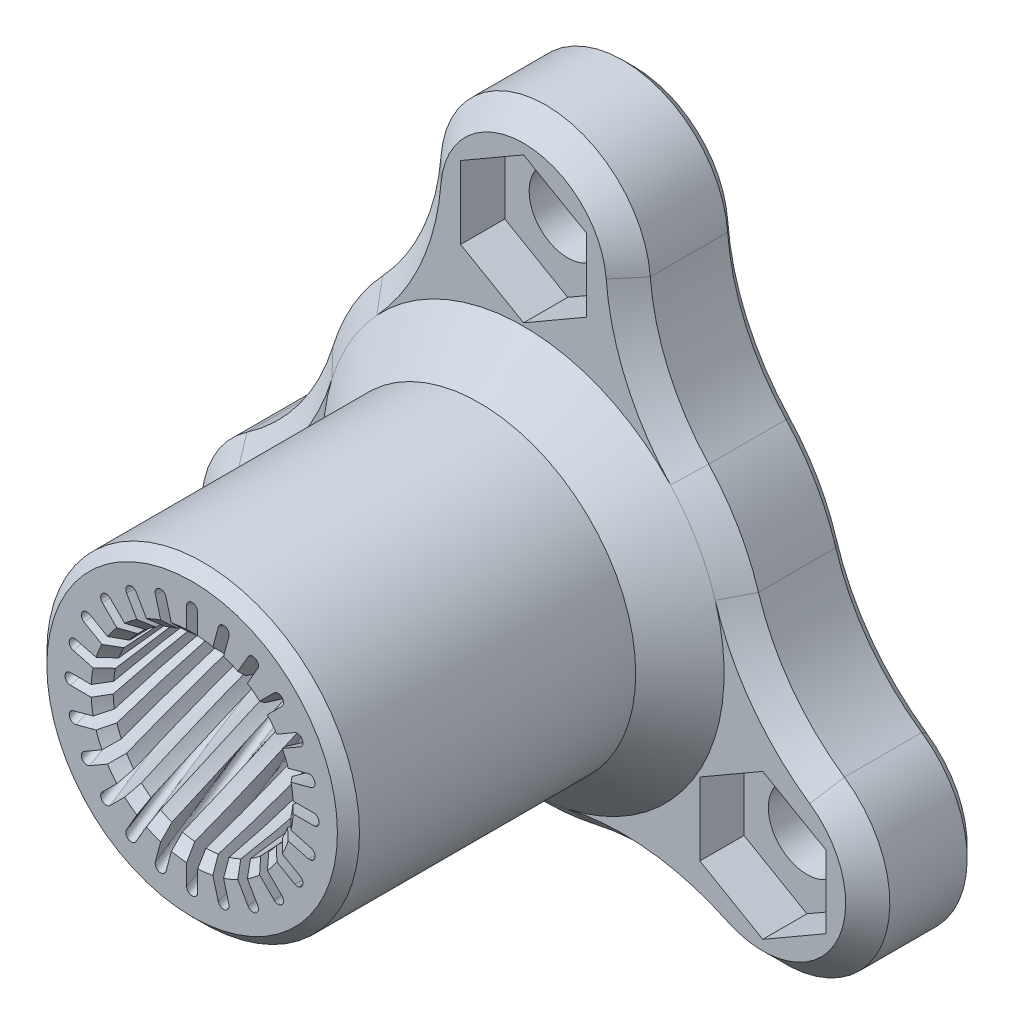
SolidWorks part; units mm, degrees
note: '?' marks a value the reader was unsure of.
ref_plane "Front Plane" through (0, 0, 0) normal (0, 0, 1) x (1, 0, 0)
ref_plane "Top Plane" through (0, 0, 0) normal (0, 1, 0) x (1, 0, 0)
ref_plane "Right Plane" through (0, 0, 0) normal (1, 0, 0) x (0, 0, -1)
sketch "Sketch1" plane through (0, 0, 0) normal (0, 0, 1) x (1, 0, 0)
  circle A0 centre (0, 0) radius 4.075
  circle A1 centre (0, 0) radius 7.075
  dimension "D1" = 8.15
  dimension "D2" = 3
extrude "Boss-Extrude1" add sketch "Sketch1" along normal blind 20
sketch "Sketch2" plane through (0, 0, 20) normal (0, 0, 1) x (1, 0, 0)
  circle A0 centre (0, 0) radius 4
curve "Helix/Spiral1" pitch 100 height 20 turns 0.2
chamfer "Chamfer3" distance 0.5 angle 45 2 edges at (4.075, 0, 20) (4.075, 0, 0)
sketch "Sketch4" plane through (0, 0, 20) normal (0, 0, 1) x (1, 0, 0)
  line L0 (3, 0) -> (5.5, 0) construction
  line L1 (3, 0.25) -> (5.5, 0.25)
  line L2 (3, -0.25) -> (5.5, -0.25)
  arc A0 (3, 0.25) -> (3, -0.25) centre (3, 0) ccw
  arc A1 (5.5, -0.25) -> (5.5, 0.25) centre (5.5, 0) ccw
  circle A2 centre (0, 0) radius 4.075 construction
  point P3 (4.25, 0)
  dimension "D1" = 3
  dimension "D2" = 2.5
  dimension "D3" = 0.5
sweep "Cut-Sweep1" cut profiles "Sketch4" path "Helix/Spiral1"
ref_axis "Axis1" through (0, 0, 20) along (0, 0, -1)?
pattern_circular "CirPattern1" count 24 every 15 about axis through (0, 0, 20) along (0, 0, -1) of "Cut-Sweep1"
sketch "Sketch5" plane through (0, 0, 0) normal (0, 0, -1) x (-1, 0, 0)
  circle A0 centre (0, 0) radius 12.5 construction
  circle A1 centre (0, 12.5) radius 1.75
  arc A2 (4.7351, 12.876) -> (-4.7351, 12.876) centre (0, 12.5) ccw
  circle A3 centre (10.8253, -6.25) radius 1.75
  arc A4 (8.7834, -10.5387) -> (13.5185, -2.3373) centre (10.8253, -6.25) ccw
  circle A5 centre (-10.8253, -6.25) radius 1.75
  arc A6 (-13.5185, -2.3373) -> (-8.7834, -10.5387) centre (-10.8253, -6.25) ccw
  circle A7 centre (0, 0) radius 7.075 construction
  circle A8 centre (0, 0) radius 7.075
  arc A9 (9.6301, 2.961) -> (7.3793, 6.8594) centre (0, 0) ccw
  circle A10 centre (0, 0) radius 10.075 construction
  arc A11 (-2.2507, -9.8204) -> (2.2507, -9.8204) centre (0, 0) ccw
  arc A12 (-7.3793, 6.8594) -> (-9.6301, 2.961) centre (0, 0) ccw
  arc A13 (9.6301, 2.961) -> (13.5185, -2.3373) centre (19.1884, 5.8999) ccw
  arc A14 (-4.7351, 12.876) -> (-7.3793, 6.8594) centre (-14.7037, 13.6677) cw
  arc A15 (-9.6301, 2.961) -> (-13.5185, -2.3373) centre (-19.1884, 5.8999) cw
  arc A16 (-2.2507, -9.8204) -> (-8.7834, -10.5387) centre (-4.4847, -19.5676) ccw
  arc A17 (2.2507, -9.8204) -> (8.7834, -10.5387) centre (4.4847, -19.5676) cw
  arc A18 (7.3793, 6.8594) -> (4.7351, 12.876) centre (14.7037, 13.6677) cw
  point P15 (0, 0)
  point P24 (-3.6056, 9.4077)
  dimension "D1" = 25
  dimension "D2" = 3.5
  dimension "D3" = 3
  dimension "D6" = 10
  dimension "D7" = 10
  dimension "D5" = 3
  dimension "D4" = 3
extrude "Boss-Extrude2" add sketch "Sketch5" against normal blind 3
sketch "Sketch6" plane through (0, 0, 3) normal (0, 0, 1) x (1, 0, 0)
  line L0 (13.6753, -7.8954) -> (13.6753, -4.6046)
  line L1 (0, 15.7909) -> (-2.85, 14.1454)
  line L2 (-2.85, 14.1454) -> (-2.85, 10.8546)
  line L3 (-2.85, 10.8546) -> (0, 9.2091)
  line L4 (0, 9.2091) -> (2.85, 10.8546)
  line L5 (2.85, 10.8546) -> (2.85, 14.1454)
  line L6 (2.85, 14.1454) -> (0, 15.7909)
  line L7 (13.6753, -4.6046) -> (10.8253, -2.9591)
  line L8 (10.8253, -2.9591) -> (7.9753, -4.6046)
  line L9 (7.9753, -4.6046) -> (7.9753, -7.8954)
  line L10 (7.9753, -7.8954) -> (10.8253, -9.5409)
  line L11 (10.8253, -9.5409) -> (13.6753, -7.8954)
  line L12 (-13.6753, -7.8954) -> (-10.8253, -9.5409)
  line L13 (-10.8253, -9.5409) -> (-7.9753, -7.8954)
  line L14 (-7.9753, -7.8954) -> (-7.9753, -4.6046)
  line L15 (-7.9753, -4.6046) -> (-10.8253, -2.9591)
  line L16 (-10.8253, -2.9591) -> (-13.6753, -4.6046)
  line L17 (-13.6753, -4.6046) -> (-13.6753, -7.8954)
  circle A0 centre (0, 12.5) radius 2.85 construction
  circle A1 centre (10.8253, -6.25) radius 2.85 construction
  circle A2 centre (-10.8253, -6.25) radius 2.85 construction
  circle A15 centre (0, 0) radius 7.075 construction
  circle A16 centre (0, 0) radius 7.075
  arc A27 (-13.5185, -2.3373) -> (-9.6301, 2.961) centre (-19.1884, 5.8999) ccw
  arc A28 (-13.5185, -2.3373) -> (-8.7834, -10.5387) centre (-10.8253, -6.25) ccw
  arc A29 (-2.2507, -9.8204) -> (-8.7834, -10.5387) centre (-4.4847, -19.5676) ccw
  arc A30 (-2.2507, -9.8204) -> (2.2507, -9.8204) centre (0, 0) ccw
  arc A31 (8.7834, -10.5387) -> (2.2507, -9.8204) centre (4.4847, -19.5676) ccw
  arc A32 (8.7834, -10.5387) -> (13.5185, -2.3373) centre (10.8253, -6.25) ccw
  arc A33 (9.6301, 2.961) -> (13.5185, -2.3373) centre (19.1884, 5.8999) ccw
  arc A34 (9.6301, 2.961) -> (7.3793, 6.8594) centre (0, 0) ccw
  arc A35 (4.7351, 12.876) -> (7.3793, 6.8594) centre (14.7037, 13.6677) ccw
  arc A36 (4.7351, 12.876) -> (-4.7351, 12.876) centre (0, 12.5) ccw
  arc A37 (-7.3793, 6.8594) -> (-4.7351, 12.876) centre (-14.7037, 13.6677) ccw
  arc A38 (-7.3793, 6.8594) -> (-9.6301, 2.961) centre (0, 0) ccw
  arc A39 (-13.5185, -2.3373) -> (-9.6301, 2.961) centre (-19.1884, 5.8999) ccw
  arc A40 (-13.5185, -2.3373) -> (-8.7834, -10.5387) centre (-10.8253, -6.25) ccw
  arc A41 (-2.2507, -9.8204) -> (-8.7834, -10.5387) centre (-4.4847, -19.5676) ccw
  arc A42 (-2.2507, -9.8204) -> (2.2507, -9.8204) centre (0, 0) ccw
  arc A43 (8.7834, -10.5387) -> (2.2507, -9.8204) centre (4.4847, -19.5676) ccw
  arc A44 (8.7834, -10.5387) -> (13.5185, -2.3373) centre (10.8253, -6.25) ccw
  arc A45 (9.6301, 2.961) -> (13.5185, -2.3373) centre (19.1884, 5.8999) ccw
  arc A46 (9.6301, 2.961) -> (7.3793, 6.8594) centre (0, 0) ccw
  arc A47 (4.7351, 12.876) -> (7.3793, 6.8594) centre (14.7037, 13.6677) ccw
  arc A48 (4.7351, 12.876) -> (-4.7351, 12.876) centre (0, 12.5) ccw
  arc A49 (-7.3793, 6.8594) -> (-4.7351, 12.876) centre (-14.7037, 13.6677) ccw
  arc A50 (-7.3793, 6.8594) -> (-9.6301, 2.961) centre (0, 0) ccw
  point P27 (0, 0)
  dimension "D1" = 5.7
  dimension "D3" = 0
  dimension "D2" = 3
extrude "Boss-Extrude3" add sketch "Sketch6" along normal blind 2
chamfer "Chamfer1" distance 2 angle 45 1 edges at (7.075, 0, 5)
chamfer "Chamfer2" distance 1 angle 45 12 edges at (0, -10.075, 5) (5.5778, -9.6276, 5) (-5.5778, -9.6276, 5) (14.9389, -8.625, 5) (-14.9389, -8.625, 5) (11.1266, -0.0167, 5) (-11.1266, -0.0167, 5) (8.7252, 5.0375, 5) (-8.7252, 5.0375, 5) (5.5488, 9.6443, 5) (-5.5488, 9.6443, 5) (0, 17.25, 5)
chamfer "Chamfer4" distance 0.5 angle 45 16 edges at (7.075, 0, 20) (-1.75, 12.5, 0) (9.0753, -6.25, 0) (-12.5753, -6.25, 0) (-5.5488, 9.6443, 0) (0, 17.25, 0) (-8.7252, 5.0375, 0) (5.5488, 9.6443, 0) (-11.1266, -0.0167, 0) (8.7252, 5.0375, 0) (-14.9389, -8.625, 0) (11.1266, -0.0167, 0) (-5.5778, -9.6276, 0) (14.9389, -8.625, 0) (0, -10.075, 0) (5.5778, -9.6276, 0)
sketch "Sketch7" plane through (0, 0, 0) normal (0, 0, -1) x (-1, 0, 0)
  circle A0 centre (0, 0) radius 8.05
  dimension "D1" = 16.1
extrude "Cut-Extrude1" [suppressed] cut sketch "Sketch7" against normal blind 2.1
